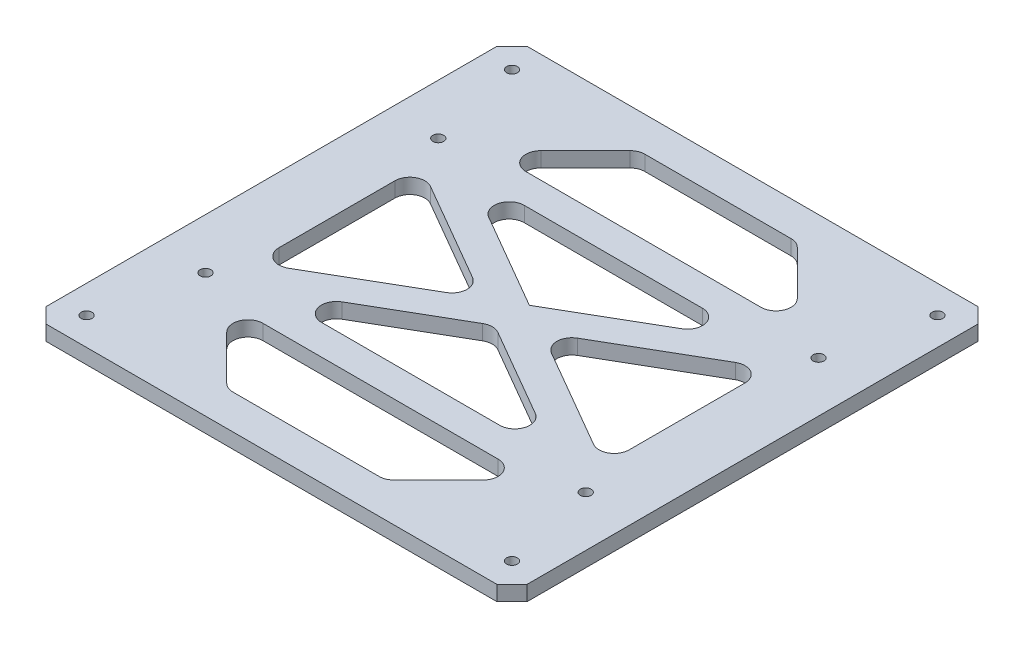
SolidWorks part; units mm, degrees
ref_plane "Front Plane" through (0, 0, 0) normal (0, 0, 1) x (1, 0, 0)
ref_plane "Top Plane" through (0, 0, 0) normal (0, 1, 0) x (1, 0, 0)
ref_plane "Right Plane" through (0, 0, 0) normal (1, 0, 0) x (0, 0, -1)
sketch "Sketch1" plane through (0, 0, 0) normal (0, 1, 0) x (1, 0, 0)
  line L0 (0, 196.85) -> (6.35, 203.2)
  line L1 (6.35, 0) -> (196.85, 0)
  line L2 (0, 6.35) -> (0, 196.85)
  line L3 (6.35, 203.2) -> (196.85, 203.2)
  line L4 (203.2, 6.35) -> (203.2, 196.85)
  line L5 (196.85, 203.2) -> (203.2, 196.85)
  line L6 (196.85, 0) -> (203.2, 6.35)
  line L7 (0, 6.35) -> (6.35, 0)
  point P0 (0, 0)
  point P1 (203.2, 203.2)
  point P2 (0, 203.2)
  point P3 (203.2, 0)
  dimension "D1" = 203.2
  dimension "D2" = 203.2
extrude "Boss-Extrude1" add sketch "Sketch1" along normal blind 6.35
sketch "Sketch3" plane through (0, 6.35, 0) normal (0, 1, 0) x (1, 0, 0)
  line L0 (6.35, 0) -> (196.85, 0) construction
  line L1 (0, 196.85) -> (0, 6.35) construction
  line L2 (203.2, 6.35) -> (203.2, 196.85) construction
  line L3 (196.85, 203.2) -> (6.35, 203.2) construction
  circle A0 centre (11.7373, 11.7373) radius 2.286
  circle A1 centre (191.4627, 11.7373) radius 2.286
  circle A2 centre (191.4627, 191.4627) radius 2.286
  circle A3 centre (11.7373, 191.4627) radius 2.286
  dimension "D1" = 2
  dimension "D3" = 4.572
  dimension "D4" = 11.7373
  dimension "D5" = 11.7373
  dimension "D6" = 11.7373
  dimension "D7" = 11.7373
  dimension "D8" = 11.7373
  dimension "D2" = 2
extrude "Cut-Extrude2" cut sketch "Sketch3" against normal through all
sketch "Sketch4" plane through (0, 6.35, 0) normal (0, 1, 0) x (1, 0, 0)
  line L0 (0, 196.85) -> (0, 6.35) construction
  line L1 (21.2903, 150.7744) -> (181.9097, 150.7744) construction
  line L2 (21.2903, 150.7744) -> (21.2903, 52.4256) construction
  line L3 (21.2903, 52.4256) -> (181.9097, 52.4256) construction
  line L4 (181.9097, 150.7744) -> (181.9097, 52.4256) construction
  line L5 (196.85, 203.2) -> (6.35, 203.2) construction
  line L6 (18.1153, 138.6191) -> (68.1095, 188.6134)
  line L7 (135.0905, 188.6134) -> (68.1095, 188.6134)
  line L8 (135.0905, 188.6134) -> (185.0847, 138.6191)
  line L9 (185.0847, 64.5809) -> (135.0905, 14.5866)
  line L10 (185.0847, 138.6191) -> (185.0847, 64.5809)
  line L11 (135.0905, 14.5866) -> (68.1095, 14.5866)
  line L12 (68.1095, 14.5866) -> (18.1153, 64.5809)
  line L13 (18.1153, 64.5809) -> (18.1153, 138.6191)
  circle A0 centre (21.2903, 150.7744) radius 2.286
  circle A1 centre (181.9097, 150.7744) radius 2.286
  circle A2 centre (181.9097, 52.4256) radius 2.286
  circle A3 centre (21.2903, 52.4256) radius 2.286
  point P6 (0, 101.6)
  point P7 (21.2903, 101.6)
  point P10 (101.6, 203.2)
  point P11 (101.6, 150.7744)
  point P26 (101.6, 203.2)
  dimension "D3" = 4.572
  dimension "D5" = 6.35
  dimension "D7" = 6.35
  dimension "D1" = 160.6194
  dimension "D2" = 98.3488
  dimension "D4" = 6.35
  dimension "D6" = 6.35
  dimension "D8" = 6.35
extrude "Cut-Extrude3" cut sketch "Sketch4" against normal through all
sketch "Sketch5" plane through (0, 6.35, 0) normal (0, 1, 0) x (1, 0, 0)
  line L0 (21.2903, 52.4256) -> (181.9097, 52.4256) construction
  line L1 (181.9097, 52.4256) -> (181.9097, 150.7744) construction
  line L2 (181.9097, 150.7744) -> (21.2903, 150.7744) construction
  line L3 (21.2903, 150.7744) -> (21.2903, 52.4256) construction
  line L4 (188.2597, 157.1244) -> (14.9403, 157.1244)
  line L5 (14.9403, 157.1244) -> (14.9403, 46.0756)
  line L6 (14.9403, 46.0756) -> (188.2597, 46.0756)
  line L7 (188.2597, 46.0756) -> (188.2597, 157.1244)
  line L8 (139.248, 144.4244) -> (63.952, 144.4244)
  line L9 (27.6403, 126.0723) -> (27.6403, 77.1277)
  line L10 (63.952, 58.7756) -> (139.248, 58.7756)
  line L11 (175.5597, 77.1277) -> (175.5597, 126.0723)
  line L12 (27.6403, 58.7756) -> (175.5597, 144.4244) construction
  line L13 (175.5597, 58.7756) -> (27.6403, 144.4244) construction
  line L14 (60.7701, 70.6209) -> (98.4181, 92.4199)
  line L15 (166.0278, 71.6325) -> (123.7631, 96.1047)
  line L16 (37.1722, 71.6325) -> (79.4369, 96.1047)
  line L17 (142.4299, 70.6209) -> (104.7819, 92.4199)
  line L18 (178.7416, 64.2709) -> (30.8222, 149.9197) construction
  line L19 (172.3778, 53.2803) -> (24.4584, 138.9291) construction
  line L20 (24.4584, 64.2709) -> (172.3778, 149.9197) construction
  line L21 (30.8222, 53.2803) -> (178.7416, 138.9291) construction
  line L22 (27.6403, 58.7756) -> (175.5597, 58.7756) construction
  line L23 (175.5597, 58.7756) -> (175.5597, 144.4244) construction
  line L24 (175.5597, 144.4244) -> (27.6403, 144.4244) construction
  line L25 (27.6403, 144.4244) -> (27.6403, 58.7756) construction
  line L26 (79.4369, 107.0953) -> (37.1722, 131.5675)
  line L27 (101.6, 108.9377) -> (142.4299, 132.5791)
  line L28 (123.7631, 107.0953) -> (166.0278, 131.5675)
  line L29 (101.6, 108.9377) -> (60.7701, 132.5791)
  circle A0 centre (181.9097, 52.4256) radius 2.286 construction
  circle A1 centre (181.9097, 150.7744) radius 2.286 construction
  circle A2 centre (21.2903, 150.7744) radius 2.286 construction
  circle A3 centre (21.2903, 52.4256) radius 2.286 construction
  circle A4 centre (181.9097, 52.4256) radius 2.286
  circle A5 centre (181.9097, 150.7744) radius 2.286
  circle A6 centre (21.2903, 150.7744) radius 2.286
  circle A7 centre (21.2903, 52.4256) radius 2.286
  arc A8 (60.7701, 132.5791) -> (63.952, 144.4244) centre (63.952, 138.0744) cw
  arc A9 (142.4299, 132.5791) -> (139.248, 144.4244) centre (139.248, 138.0744) ccw
  arc A10 (166.0278, 131.5675) -> (175.5597, 126.0723) centre (169.2097, 126.0723) cw
  arc A11 (123.7631, 107.0953) -> (123.7631, 96.1047) centre (126.945, 101.6) ccw
  arc A12 (166.0278, 71.6325) -> (175.5597, 77.1277) centre (169.2097, 77.1277) ccw
  arc A13 (142.4299, 70.6209) -> (139.248, 58.7756) centre (139.248, 65.1256) cw
  arc A14 (104.7819, 92.4199) -> (98.4181, 92.4199) centre (101.6, 86.9247) ccw
  arc A15 (79.4369, 107.0953) -> (79.4369, 96.1047) centre (76.255, 101.6) cw
  arc A16 (37.1722, 131.5675) -> (27.6403, 126.0723) centre (33.9903, 126.0723) ccw
  arc A17 (37.1722, 71.6325) -> (27.6403, 77.1277) centre (33.9903, 77.1277) cw
  arc A18 (60.7701, 70.6209) -> (63.952, 58.7756) centre (63.952, 65.1256) ccw
  dimension "D5" = 6.35
  dimension "D1" = 6.35
  dimension "D3" = 6.35
  dimension "D2" = 6.35
  dimension "D4" = 6.35
extrude "Boss-Extrude2" add sketch "Sketch5" against normal up to surface (6.35 mm away) up to face at (181.9097, 0, -148.4884)
fillet "Fillet1" radius 6.35 8 edges at (135.0905, 3.175, -188.6134) (68.1095, 3.175, -188.6134) (36.6205, 3.175, -157.1244) (166.5795, 3.175, -157.1244) (68.1095, 3.175, -14.5866) (36.6205, 3.175, -46.0756) (135.0905, 3.175, -14.5866) (166.5795, 3.175, -46.0756)
